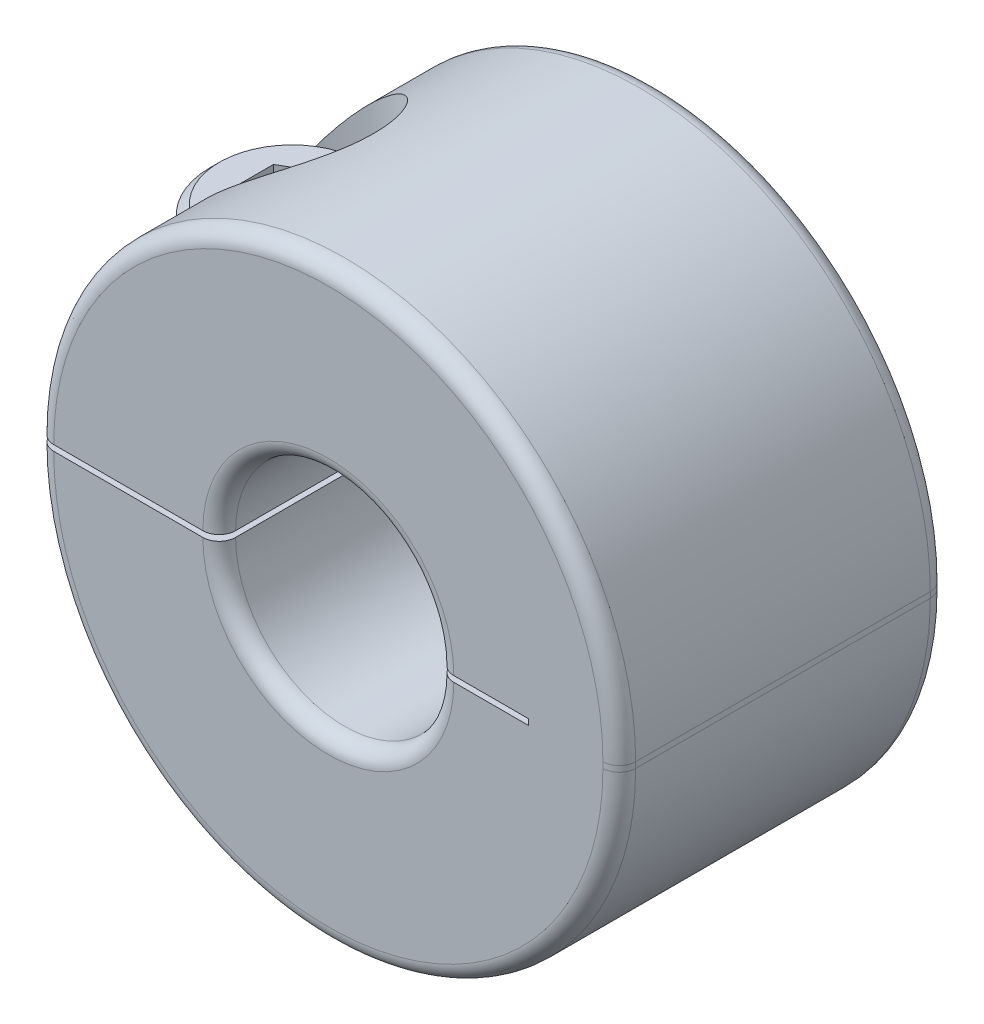
SolidWorks part; units mm, degrees
ref_plane "Front Plane" through (0, 0, 0) normal (0, 0, 1) x (1, 0, 0)
ref_plane "Top Plane" through (0, 0, 0) normal (0, 1, 0) x (1, 0, 0)
ref_plane "Right Plane" through (0, 0, 0) normal (1, 0, 0) x (0, 0, -1)
sketch "Sketch1" plane through (0, 0, 0) normal (0, 0, 1) x (1, 0, 0)
  line L0 (-8, 0) -> (-3, 0) construction
  line L1 (-8, 0.08) -> (-3, 0.08)
  line L2 (-8, -0.08) -> (-3, -0.08)
  line L3 (3, 0.08) -> (8, 0.08) construction
  line L4 (3, -0.08) -> (8, -0.08) construction
  line L5 (0, 0) -> (0, 8) construction
  line L6 (8, 0.08) -> (8, -0.08)
  line L7 (3, 0.08) -> (5.5, 0.08)
  line L8 (5.5, 0.08) -> (5.5, -0.08)
  line L10 (5.5, -0.08) -> (3, -0.08)
  circle A0 centre (0, 0) radius 8 construction
  circle A1 centre (0, 0) radius 3 construction
  arc A2 (-8, 0.08) -> (8, 0.08) centre (0, 0.08) cw
  arc A3 (-8, -0.08) -> (8, -0.08) centre (0, -0.08) ccw
  arc A4 (-3, 0.08) -> (3, 0.08) centre (0, 0.08) cw
  arc A5 (-3, -0.08) -> (3, -0.08) centre (0, -0.08) ccw
  point P4 (8, 0)
  dimension "Bore Dia" = 6
  dimension "OD" = 16
  dimension "Separation" = 0.16
extrude "Extrude1" add sketch "Sketch1" along normal mid plane 9
sketch "Sketch4" plane through (0, 0, 0) normal (0, 0, 1) x (1, 0, 0)
  line L0 (-5.5, 8.08) -> (-3.25, 8.08)
  line L1 (-3.25, 8.08) -> (-3.25, 1.58)
  line L2 (-3.25, 1.58) -> (-4, 1.58)
  line L3 (-4, 1.58) -> (-4, -8.08)
  line L4 (-4, -8.08) -> (-5.5, -8.08)
  line L5 (-5.5, -8.08) -> (-5.5, 8.08)
  line L6 (-3.25, 4.58) -> (-7.75, 4.58) construction
  line L7 (-5.5, 8.08) -> (-5.5, 10.62) construction
  line L8 (-3.25, 8.08) -> (0, 8.08) construction
  line L9 (0, -8.08) -> (-4, -8.08) construction
  line L10 (-8, 0) -> (-3, 0) construction
  line L11 (-8, 0.08) -> (-3, 0.08) construction
  circle A0 centre (0, 0) radius 8 construction
  arc A1 (8, 0.08) -> (-8, 0.08) centre (0, 0.08) ccw construction
  circle A2 centre (0, 0) radius 3 construction
  arc A3 (-8, -0.08) -> (8, -0.08) centre (0, -0.08) ccw construction
  point P13 (-5.5, 0)
  point P19 (-5.5, 0)
  point P20 (-5.5, 4.58)
  dimension "D1" = 3
  dimension "D2" = 5
  dimension "D3" = 1.5
  dimension "D4" = 4.5
  dimension "D5" = 2.54
  dimension "Screw Dia" = 3
revolve "Cut-Revolve1" cut sketch "Sketch4" angle 360 about L5
sketch "Sketch6" plane through (0, 0, 0) normal (0, 0, 1) x (1, 0, 0)
  line L0 (-5.5, 4.58) -> (-3.25, 4.58)
  line L1 (-3.25, 4.58) -> (-7.75, 4.58) construction
  line L2 (-3.25, 4.58) -> (-3.25, 1.58)
  line L3 (-3.25, 1.58) -> (-4, 1.58)
  line L4 (-4, 1.58) -> (-4, -4.42)
  line L5 (-4, 1.58) -> (-4, -8.08) construction
  line L6 (-4, -4.42) -> (-5.5, -4.42)
  line L7 (-5.5, -8.08) -> (-5.5, 8.08) construction
  line L8 (-5.5, -4.42) -> (-5.5, 4.58)
  line L9 (-4, -4.42) -> (-7, -4.42) construction
  dimension "Head Ht" = 3
  dimension "Screw Lg" = 9
revolve "Revolve1" add sketch "Sketch6" angle 360 about L8
sketch "Sketch7" plane through (0, 4.58, 0) normal (0, 1, 0) x (-1, 0, 0)
  line L1 (5.5, -1.3856) -> (6.7, -0.6928)
  line L2 (6.7, -0.6928) -> (6.7, 0.6928)
  line L3 (6.7, 0.6928) -> (5.5, 1.3856)
  line L4 (5.5, 1.3856) -> (4.3, 0.6928)
  line L5 (4.3, 0.6928) -> (4.3, -0.6928)
  line L6 (4.3, -0.6928) -> (5.5, -1.3856)
  circle A0 centre (5.5, 0) radius 1.2 construction
  dimension "D1" = 2.4
extrude "Cut-Extrude2" cut sketch "Sketch7" against normal blind 1.5
fillet "Fillet1" radius 0.45 8 edges at (0, 3.08, -4.5) (0, 3.08, 4.5) (0, 8.08, -4.5) (0, 8.08, 4.5) (0, -8.08, -4.5) (0, -8.08, 4.5) (8, 0, -4.5) (8, 0, 4.5)
fillet "Fillet2" radius 0.45 2 edges at (0, -3.08, -4.5) (0, -3.08, 4.5)
chamfer "Chamfer2" distance 0.254 angle 45 1 edges at (-5.5, 4.58, -2.25)
equation "\"D1@Sketch4\" = \"Screw Dia@Sketch4\""
equation "\"D4@Sketch4\" = \"Screw Dia@Sketch4\"*1.5"
equation "\"D1@Sketch7\" = \"Screw Dia@Sketch4\"*.8"
equation "\"D1@Cut-Extrude2\" = \"Head Ht@Sketch6\"/2"
equation "\"D3@Sketch4\" = \"D1@Sketch4\"*.5"
equation "\"D1@Fillet1\" = \"Width@Extrude1\"*.05"
equation "\"D1@Fillet2\" = \"D1@Fillet1\""
equation "\"Screw Lg@Sketch6\" = \"Head Ht@Sketch6\"*3"
equation "\"Separation@Sketch1\" = \"OD@Sketch1\"*.01"
